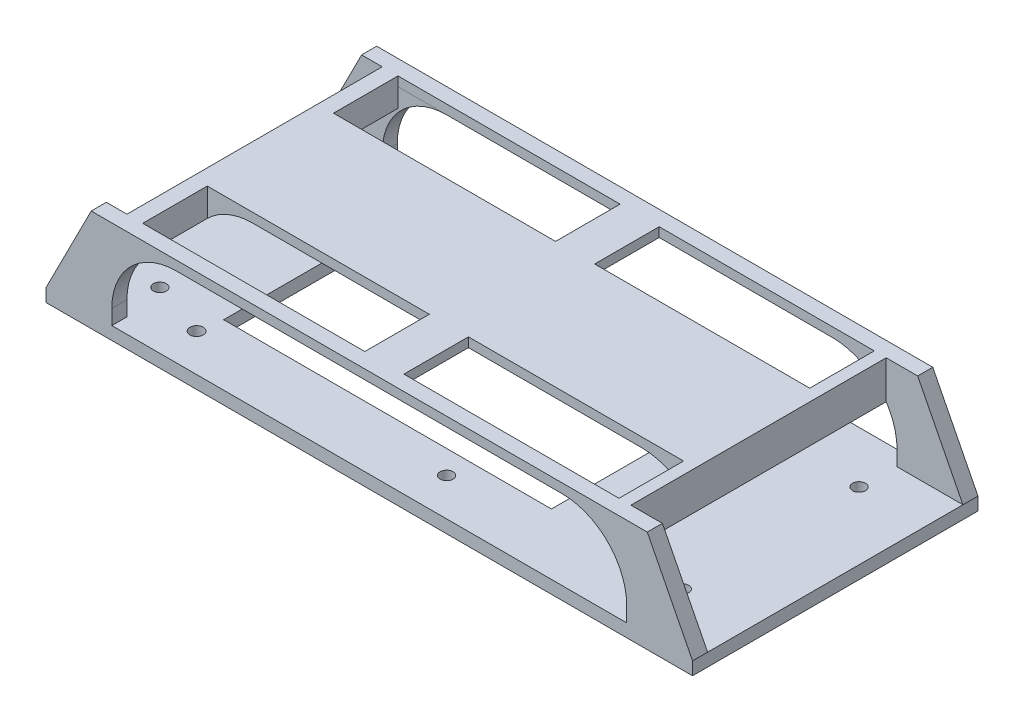
SolidWorks part; units mm, degrees
ref_plane "前视基准面" through (0, 0, 0) normal (0, 0, 1) x (1, 0, 0)
ref_plane "上视基准面" through (0, 0, 0) normal (0, 1, 0) x (1, 0, 0)
ref_plane "右视基准面" through (0, 0, 0) normal (1, 0, 0) x (0, 0, -1)
sketch "草图1" plane through (0, 0, 0) normal (0, 1, 0) x (1, 0, 0)
  line L1 (-75, -50) -> (75, -50)
  line L2 (-75, -50) -> (-75, 50)
  line L3 (-75, 50) -> (75, 50)
  line L4 (75, -50) -> (75, 50)
  line L5 (-75, -50) -> (75, 50) construction
  line L6 (-75, 50) -> (75, -50) construction
  point P0 (0, 0)
  dimension "D1" = 150
  dimension "D2" = 100
extrude "凸台-拉伸1" add sketch "草图1" along normal blind 3
sketch "草图2" plane through (0, 3, 0) normal (0, 1, 0) x (1, 0, 0)
  line L0 (-75, 25.451) -> (82.4386, 25.451)
  line L1 (-75, 50) -> (-75, -50) construction
  line L2 (82.4386, 25.451) -> (82.4386, 50)
  line L3 (82.4386, 50) -> (45.2438, 69.0177)
  line L4 (45.2438, 69.0177) -> (-35.1901, 62.5086)
  line L5 (-35.1901, 62.5086) -> (-89.1493, 58.1419)
  line L6 (-89.1493, 63.5569) -> (-89.1493, -51.4431) construction
  line L7 (-89.1493, 58.1419) -> (-75, 25.451)
extrude "切除-拉伸1" cut sketch "草图2" against normal blind 10
sketch "草图4" plane through (0, 3, 0) normal (0, 1, 0) x (1, 0, 0)
  circle A0 centre (59.3704, 4.2564) radius 1.5 construction
  circle A1 centre (59.3704, -36.7436) radius 1.5 construction
  circle A2 centre (-61.8374, -36.7436) radius 1.5 construction
  circle A3 centre (-61.8374, 4.2564) radius 1.5 construction
  circle A4 centre (59.3704, 4.2564) radius 1.5
  circle A5 centre (59.3704, -36.7436) radius 1.5
  circle A6 centre (-61.8374, -36.7436) radius 1.5
  circle A7 centre (-61.8374, 4.2564) radius 1.5
extrude "切除-拉伸2" cut sketch "草图4" against normal blind 10
sketch "草图5" plane through (0, 3, 0) normal (0, 1, 0) x (1, 0, 0)
  line L0 (-75, 16.2294) -> (82.2709, 16.2294)
  line L1 (-75, 25.451) -> (-75, -50) construction
  line L2 (82.2709, 16.2294) -> (82.2709, 33.668)
  line L3 (82.2709, 33.668) -> (-81.616, 33.668)
  line L4 (-81.616, 33.668) -> (-81.616, 16.2294)
  line L5 (-81.616, 16.2294) -> (-75, 16.2294)
extrude "切除-拉伸3" cut sketch "草图5" against normal blind 10
sketch "草图6" plane through (0, 0, 50) normal (0, 0, 1) x (1, 0, 0)
  line L0 (0, 46.5106) -> (0, -56.6768) construction
  line L1 (-75, 3) -> (-64.5049, 23.6365)
  line L2 (-64.5049, 23.6365) -> (-59.7267, 23.6365)
  line L3 (-59.7267, 23.6365) -> (-59.7267, 3)
  line L4 (-75, 3) -> (75, 3) construction
  line L5 (-59.7267, 3) -> (-75, 3)
  line L6 (59.7267, 23.6365) -> (59.7267, 3)
  line L7 (64.5049, 23.6365) -> (59.7267, 23.6365)
  line L8 (75, 3) -> (64.5049, 23.6365)
  line L9 (59.7267, 3) -> (75, 3)
extrude "凸台-拉伸2" add sketch "草图6" against normal up to surface (66.2294 mm away) up to face at (0, 1.5, -16.2294)
sketch "草图8" plane through (59.7267, 0, 0) normal (-1, 0, 0) x (0, 0, 1)
  line L0 (16.8853, 3) -> (16.8853, 31.8153) construction
  line L1 (-16.2294, 3) -> (50, 3) construction
  line L2 (-12.7294, 3) -> (-12.7294, 23.6365)
  line L3 (-16.2294, 23.6365) -> (50, 23.6365) construction
  line L4 (-12.7294, 23.6365) -> (13.3853, 23.6365)
  line L5 (13.3853, 23.6365) -> (13.3853, 3)
  line L6 (13.3853, 3) -> (-12.7294, 3)
  line L7 (20.3853, 23.6365) -> (20.3853, 3)
  line L8 (46.5, 23.6365) -> (20.3853, 23.6365)
  line L9 (46.5, 3) -> (46.5, 23.6365)
  line L10 (20.3853, 3) -> (46.5, 3)
  line L11 (-16.2294, 3) -> (-16.2294, 23.6365) construction
  dimension "D1" = 3.5
  dimension "D2" = 7
extrude "切除-拉伸4" cut sketch "草图8" against normal blind 24 and the other way blind 214
sketch "草图11" plane through (0, 0, 0) normal (0, -1, 0) x (1, 0, 0)
  circle A0 centre (-48.7906, 41.2706) radius 1.55
  circle A1 centre (9.2094, 41.2706) radius 1.5
  circle A2 centre (-48.7906, -8.7294) radius 1.55
  circle A3 centre (9.2094, -8.7294) radius 1.5
extrude "切除-拉伸5" cut sketch "草图11" against normal blind 27
sketch "草图12" plane through (0, 0, 50) normal (0, 0, 1) x (1, 0, 0)
  line L0 (-59.7267, 21.4625) -> (59.7267, 21.4625)
  line L1 (-59.7267, 3) -> (-59.7267, 23.6365) construction
  line L2 (59.7267, 23.6365) -> (59.7267, 3) construction
  line L3 (59.7267, 21.4625) -> (59.7267, 23.6365)
  line L4 (59.7267, 23.6365) -> (-59.7267, 23.6365)
  line L5 (-59.7267, 23.6365) -> (-59.7267, 21.4625)
extrude "凸台-拉伸3" add sketch "草图12" against normal up to surface (66.2294 mm away) up to face at (0, 10.6546, -16.2294)
sketch "草图13" plane through (0, 23.6365, 0) normal (0, 1, 0) x (1, 0, 0)
  line L0 (-64.5049, 12.7294) -> (-64.5049, -13.3853)
  line L1 (-64.5049, -13.3853) -> (-59.7267, -13.3853)
  line L2 (-59.7267, -13.3853) -> (-59.7267, 12.7294)
  line L3 (-59.7267, 12.7294) -> (-64.5049, 12.7294)
  line L4 (-75, -16.8853) -> (78.9084, -16.8853) construction
  line L5 (-75, -13.3853) -> (-75, -20.3853) construction
  line L6 (0, 21.4381) -> (0, -57.3466) construction
  line L7 (-59.7267, -46.5) -> (-64.5049, -46.5)
  line L8 (-59.7267, -20.3853) -> (-59.7267, -46.5)
  line L9 (-64.5049, -20.3853) -> (-59.7267, -20.3853)
  line L10 (-64.5049, -46.5) -> (-64.5049, -20.3853)
  line L11 (64.5049, -46.5) -> (64.5049, -20.3853)
  line L12 (64.5049, -20.3853) -> (59.7267, -20.3853)
  line L13 (59.7267, -20.3853) -> (59.7267, -46.5)
  line L14 (59.7267, -46.5) -> (64.5049, -46.5)
  line L15 (59.7267, 12.7294) -> (64.5049, 12.7294)
  line L16 (59.7267, -13.3853) -> (59.7267, 12.7294)
  line L17 (64.5049, -13.3853) -> (59.7267, -13.3853)
  line L18 (64.5049, 12.7294) -> (64.5049, -13.3853)
extrude "凸台-拉伸4" add sketch "草图13" against normal up to surface (2.174 mm away) up to face at (0, 21.4625, 16.8853)
sketch "草图14" plane through (0, 23.6365, 0) normal (0, 1, 0) x (1, 0, 0)
  line L4 (0, 23.0896) -> (0, -50) construction
  line L5 (64.5049, -50) -> (-64.5049, -50) construction
  line L6 (-64.5049, -16.8853) -> (64.5049, -16.8853) construction
  line L7 (-64.5049, -13.3853) -> (-64.5049, -20.3853) construction
  line L8 (64.5049, -13.3853) -> (64.5049, -20.3853) construction
  line L10 (-59.7267, 12.7294) -> (-4.5371, 12.7294)
  line L11 (-4.5371, 12.7294) -> (-4.5371, -2.2442)
  line L12 (-59.7267, 12.7294) -> (-64.5049, 12.7294)
  line L14 (-64.5049, 12.7294) -> (-64.5049, -2.2442)
  line L15 (-64.5049, 12.7294) -> (-64.5049, -13.3853) construction
  line L16 (-64.5049, -2.2442) -> (-4.5371, -2.2442)
  line L17 (64.5049, -2.2442) -> (4.5371, -2.2442)
  line L18 (64.5049, 12.7294) -> (64.5049, -2.2442)
  line L19 (59.7267, 12.7294) -> (64.5049, 12.7294)
  line L20 (4.5371, 12.7294) -> (4.5371, -2.2442)
  line L21 (59.7267, 12.7294) -> (4.5371, 12.7294)
  line L22 (59.7267, -46.5) -> (4.5371, -46.5)
  line L23 (4.5371, -46.5) -> (4.5371, -31.5264)
  line L24 (59.7267, -46.5) -> (64.5049, -46.5)
  line L25 (64.5049, -46.5) -> (64.5049, -31.5264)
  line L26 (64.5049, -31.5264) -> (4.5371, -31.5264)
  line L27 (-64.5049, -31.5264) -> (-4.5371, -31.5264)
  line L28 (-64.5049, -46.5) -> (-64.5049, -31.5264)
  line L29 (-59.7267, -46.5) -> (-64.5049, -46.5)
  line L30 (-4.5371, -46.5) -> (-4.5371, -31.5264)
  line L31 (-59.7267, -46.5) -> (-4.5371, -46.5)
extrude "切除-拉伸6" cut sketch "草图14" along direction (0, -1, 0) on the side against the normal up to surface (2.174 mm away) up to face at (0, 21.4625, 16.8853)
sketch "草图16" plane through (0, 0, 20.3853) normal (0, 0, 1) x (1, 0, 0)
  line L0 (-64.5049, 23.6365) -> (-75, 3)
  line L1 (-75, 3) -> (-59.7267, 3)
  line L2 (-59.7267, 3) -> (-59.7267, 23.6365)
  line L4 (64.5049, 23.6365) -> (-64.5049, 23.6365) construction
  line L5 (-59.7267, 23.6365) -> (-64.5049, 23.6365)
  line L6 (0, 30.8415) -> (0, -19.8881) construction
  line L7 (59.7267, 23.6365) -> (64.5049, 23.6365)
  line L8 (59.7267, 3) -> (59.7267, 23.6365)
  line L9 (75, 3) -> (59.7267, 3)
  line L10 (64.5049, 23.6365) -> (75, 3)
extrude "切除-拉伸8" cut sketch "草图16" against normal up to surface (7 mm away) up to face at (-64.6926, 14.5123, 13.3853)
sketch "草图18" plane through (0, 0, 31.5264) normal (0, 0, 1) x (1, 0, 0)
  line L0 (-59.7267, 23.6365) -> (-59.7267, 21.4625)
  line L1 (-59.7267, 21.4625) -> (-64.5049, 21.4625)
  line L2 (-64.5049, 21.4625) -> (-64.5049, 23.6365)
  line L3 (64.5049, 23.6365) -> (-64.5049, 23.6365) construction
  line L4 (-64.5049, 21.4625) -> (-64.5049, 23.6365) construction
  line L5 (-64.5049, 23.6365) -> (-59.7267, 23.6365)
  line L6 (0, 29.1132) -> (0, -18.6682) construction
  line L7 (64.5049, 23.6365) -> (59.7267, 23.6365)
  line L8 (64.5049, 21.4625) -> (64.5049, 23.6365)
  line L9 (59.7267, 21.4625) -> (64.5049, 21.4625)
  line L10 (59.7267, 23.6365) -> (59.7267, 21.4625)
extrude "切除-拉伸9" cut sketch "草图18" against normal up to surface (29.2821 mm away) up to face at (-34.521, 22.5495, 2.2442)
sketch "草图19" plane through (0, 0, -12.7294) normal (0, 0, 1) x (1, 0, 0)
  line L0 (-59.7267, 23.6365) -> (-59.7267, 21.4625)
  line L1 (-59.7267, 21.4625) -> (-56.0612, 21.4625)
  line L2 (-59.7267, 21.4625) -> (59.7267, 21.4625) construction
  line L3 (-56.0612, 21.4625) -> (-56.0612, 23.6365)
  line L4 (64.5049, 23.6365) -> (-64.5049, 23.6365) construction
  line L5 (-56.0612, 23.6365) -> (-59.7267, 23.6365)
  line L6 (0, 31.9101) -> (0, -16.341) construction
extrude "凸台-拉伸7" add sketch "草图19" along normal up to surface (59.2294 mm away) up to face at (-44.6721, 16.033, 46.5)
sketch "草图20" plane through (0, 23.6365, 0) normal (0, 1, 0) x (1, 0, 0)
  line L0 (54.4369, 12.7294) -> (54.4369, -2.2442)
  line L1 (64.5049, 12.7294) -> (4.5371, 12.7294) construction
  line L2 (4.5371, -2.2442) -> (59.7267, -2.2442) construction
  line L3 (54.4369, -2.2442) -> (57.1992, -2.2442)
  line L4 (57.1992, -2.2442) -> (57.1992, 12.7294)
  line L5 (57.1992, 12.7294) -> (54.4369, 12.7294)
  line L6 (59.7267, -16.8853) -> (3.2788, -16.8853) construction
  line L8 (59.7267, -2.2442) -> (59.7267, -31.5264) construction
  line L9 (57.1992, -46.5) -> (54.4369, -46.5)
  line L10 (57.1992, -31.5264) -> (57.1992, -46.5)
  line L11 (54.4369, -31.5264) -> (57.1992, -31.5264)
  line L12 (54.4369, -46.5) -> (54.4369, -31.5264)
extrude "凸台-拉伸8" add sketch "草图20" against normal up to surface (2.174 mm away) up to face at (-30.2992, 21.4625, -5.2426)
sketch "草图21" plane through (0, 23.6365, 0) normal (0, 1, 0) x (1, 0, 0)
  line L0 (57.1992, -2.2442) -> (57.1992, -31.5264)
  line L1 (57.1992, -2.2442) -> (59.7267, -2.2442) construction
  line L2 (57.1992, -31.5264) -> (62.0456, -31.5264)
  line L3 (62.0456, -31.5264) -> (62.0456, -2.2442)
  line L4 (62.0456, -2.2442) -> (57.1992, -2.2442)
extrude "切除-拉伸10" cut sketch "草图21" against normal up to surface (2.174 mm away) up to face at (29.487, 21.4625, -5.2426)
fillet "圆角3" radius 15 3 edges at (-59.7267, 21.4625, -14.4794) (59.7267, 21.4625, 48.25) (-59.7267, 21.4625, 48.25)
sketch "草图22" plane through (0, 0, -12.7294) normal (0, 0, 1) x (1, 0, 0)
  line L0 (-59.7267, 21.4625) -> (-59.7267, 17.1254)
  line L1 (-56.0612, 21.4625) -> (-56.0612, 17.1254)
  line L2 (-56.0612, 21.4625) -> (-59.7267, 21.4625) construction
  line L3 (-56.0612, 17.1254) -> (-59.7267, 17.1254)
  line L4 (-59.7267, 21.4625) -> (-56.0612, 21.4625)
extrude "凸台-拉伸9" add sketch "草图22" along normal up to surface (59.2294 mm away) up to face at (-60.2883, 15.9037, 46.5)
fillet "圆角4" radius 15 1 edges at (-56.0612, 21.4625, 16.8853)
sketch "草图23" plane through (0, 0, 0) normal (0, -1, 0) x (1, 0, 0)
  line L0 (-47.9339, 35.8454) -> (28.1097, 35.8454)
  line L1 (28.1097, 35.8454) -> (28.1097, -2.2781)
  line L2 (28.1097, -2.2781) -> (-47.9339, -2.2781)
  line L3 (-47.9339, -2.2781) -> (-47.9339, 35.8454)
extrude "切除-拉伸11" cut sketch "草图23" against normal blind 8
